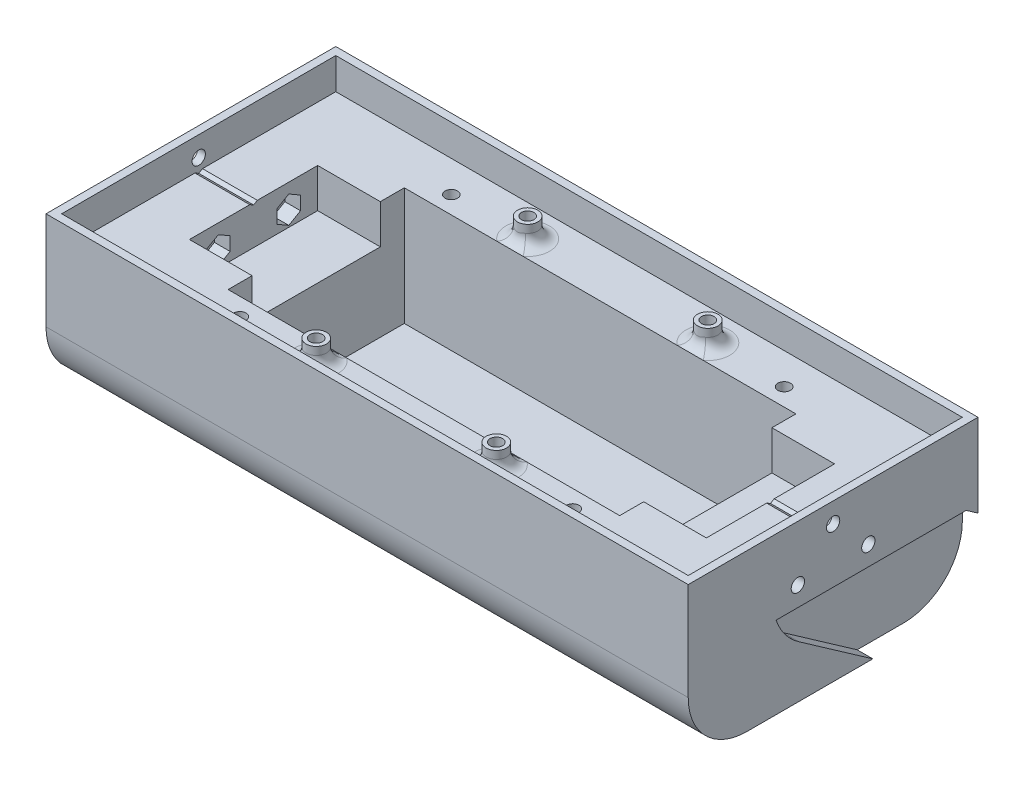
SolidWorks part; units mm, degrees
note: The reader was unsure of these and kept them because the rebuilt part matched: shared geometry of "Sketch2<3>", "Sketch2<4>", "Sketch2<5>", "Sketch4<7>", "Sketch4<4>", "Sketch4<5>", "Sketch4<6>", "Sketch4<8>", "Sketch4<9>".
ref_plane "Front Plane" through (0, 0, 0) normal (0, 0, 1) x (1, 0, 0)
ref_plane "Top Plane" through (0, 0, 0) normal (0, 1, 0) x (1, 0, 0)
ref_plane "Right Plane" through (0, 0, 0) normal (1, 0, 0) x (0, 0, -1)
sketch "Sketch2" plane through (0, 0, 0) normal (0, 1, 0) x (1, 0, 0)
  line L1 (-50, 22.5) -> (50, 22.5)
  line L2 (-50, 22.5) -> (-50, -22.5)
  line L3 (-50, -22.5) -> (50, -22.5)
  line L4 (50, 22.5) -> (50, -22.5)
  line L8 (-82, 37) -> (-82, -37)
  line L9 (-80, 35) -> (80, 35)
  line L10 (-80, 35) -> (-80, -35)
  line L11 (-80, -35) -> (80, -35)
  line L12 (80, 35) -> (80, -35)
  line L13 (-23, 27) -> (23, 27) construction
  line L14 (-23, 27) -> (-23, -27) construction
  line L15 (-23, -27) -> (23, -27) construction
  line L16 (23, 27) -> (23, -27) construction
  line L17 (-82, -37) -> (82, -37)
  line L18 (82, 37) -> (82, -37)
  line L19 (-82, 37) -> (82, 37)
  circle A0 centre (-23, 27) radius 1.6
  circle A1 centre (23, 27) radius 1.6
  circle A2 centre (23, -27) radius 1.6
  circle A3 centre (-23, -27) radius 1.6
  circle A4 centre (-23, 27) radius 2.6
  circle A5 centre (23, 27) radius 2.6
  circle A6 centre (23, -27) radius 2.6
  circle A7 centre (-23, -27) radius 2.6
  point P4 (0, 22.5)
  point P6 (-50, 0)
  point P11 (0, 35)
  point P12 (-80, 0)
  point P17 (0, 27)
  point P18 (-23, 0)
  dimension "D7" = 3.2
  dimension "D8" = 3.2
  dimension "D9" = 3.2
  dimension "D10" = 3.2
  dimension "D1" = 100
  dimension "D2" = 45
  dimension "D3" = 70
  dimension "D4" = 160
  dimension "D5" = 54
  dimension "D6" = 46
  dimension "D11" = 1
  dimension "D12" = 2
extrude "Boss-Extrude1" add sketch "Sketch2" along normal blind 40 contours L17 L18 L19 L8
extrude "Cut-Extrude1" cut sketch "Sketch2<3>" along normal through all from offset 2 contours L4 L1 L2 L3
sketch "Sketch2<3>" plane through (0, 0, 0) normal (0, 1, 0) x (1, 0, 0) same geometry as "Sketch2"
extrude "Cut-Extrude2" cut sketch "Sketch2<4>" against normal blind 8 from surface at 40 contours L11 L12 L9 L10 starting at face at (0, 40, 0)
sketch "Sketch2<4>" plane through (0, 0, 0) normal (0, 1, 0) x (1, 0, 0) same geometry as "Sketch2"
extrude "Boss-Extrude2" add sketch "Sketch2<5>" along normal blind 5 from surface at 32 contours A7 A3 | A6 A2 | A5 A1 | A4 A0 starting at face at (0, 32, 0)
sketch "Sketch2<5>" plane through (0, 0, 0) normal (0, 1, 0) x (1, 0, 0) same geometry as "Sketch2"
sketch "Sketch4" plane through (0, 0, 0) normal (1, 0, 0) x (0, 0, -1)
  line L0 (109.7184, -50.918) -> (0, 25.9077) construction
  line L1 (100.8853, -63.5329) -> (-8.8331, 13.2927)
  line L2 (118.5515, -38.303) -> (8.8331, 38.5226)
  line L3 (-9, 25.9077) -> (9, 25.9077) construction
  line L4 (-37, 0) -> (37, 0)
  line L5 (-37, 0) -> (-37, 20.9077)
  line L6 (-37, 20.9077) -> (37, 20.9077)
  line L7 (37, 0) -> (37, 20.9077)
  line L9 (0, 38.3718) -> (-3, 36.6397)
  line L10 (-3, 36.6397) -> (-3, 33.1756)
  line L11 (-3, 33.1756) -> (0, 31.4436)
  line L12 (0, 31.4436) -> (3, 33.1756)
  line L13 (3, 33.1756) -> (3, 36.6397)
  line L14 (3, 36.6397) -> (0, 38.3718)
  line L15 (9, 29.3718) -> (6, 27.6397)
  line L16 (6, 27.6397) -> (6, 24.1756)
  line L17 (6, 24.1756) -> (9, 22.4436)
  line L18 (9, 22.4436) -> (12, 24.1756)
  line L19 (12, 24.1756) -> (12, 27.6397)
  line L20 (12, 27.6397) -> (9, 29.3718)
  line L21 (-9, 29.3718) -> (-12, 27.6397)
  line L22 (-12, 27.6397) -> (-12, 24.1756)
  line L23 (-12, 24.1756) -> (-9, 22.4436)
  line L24 (-9, 22.4436) -> (-6, 24.1756)
  line L25 (-6, 24.1756) -> (-6, 27.6397)
  line L26 (-6, 27.6397) -> (-9, 29.3718)
  arc A0 (100.8853, -63.5329) -> (118.5515, -38.303) centre (109.7184, -50.918) ccw
  arc A1 (8.8331, 38.5226) -> (-8.8331, 13.2927) centre (0, 25.9077) ccw
  circle A2 centre (0, 34.9077) radius 1.7
  circle A3 centre (9, 25.9077) radius 1.7
  circle A4 centre (-9, 25.9077) radius 1.7
  circle A5 centre (0, 34.9077) radius 3 construction
  circle A6 centre (9, 25.9077) radius 3 construction
  circle A7 centre (-9, 25.9077) radius 3 construction
  point P2 (54.8592, -12.5052)
  point P17 (0, 25.9077)
  dimension "D4" = 3.4
  dimension "D5" = 3.4
  dimension "D6" = 15.4
  dimension "D8" = 3.4
  dimension "D9" = 6
  dimension "D10" = 6
  dimension "D11" = 6
  dimension "D1" = 5
  dimension "D2" = 9
  dimension "D3" = 9
  dimension "D7" = 35
extrude "Cut-Extrude3" cut sketch "Sketch4" against normal blind 4 from surface at 82 contours L6 A1 L1 L4 L2
extrude "Cut-Extrude7" cut sketch "Sketch4<7>" along normal blind 4 from surface at -82 contours L6 A1 L1 L4 L7 L2 starting at face at (-82, 20, 0)
sketch "Sketch4<7>" plane through (0, 0, 0) normal (1, 0, 0) x (0, 0, -1) same geometry as "Sketch4"
sketch "Sketch5" plane through (0, 32, 0) normal (0, 1, 0) x (1, 0, 0)
  line L0 (-80, -35) -> (-80, 35) construction
  line L1 (-66, 16.3738) -> (66, 16.3738)
  line L2 (-66, 16.3738) -> (-66, -16.3738)
  line L3 (-66, -16.3738) -> (66, -16.3738)
  line L4 (66, 16.3738) -> (66, -16.3738)
  line L6 (-42.5, 27) -> (42.5, 27) construction
  line L7 (-42.5, 27) -> (-42.5, -27) construction
  line L8 (-42.5, -27) -> (42.5, -27) construction
  line L9 (42.5, 27) -> (42.5, -27) construction
  circle A0 centre (-42.5, 27) radius 1.6
  circle A1 centre (42.5, 27) radius 1.6
  circle A2 centre (42.5, -27) radius 1.6
  circle A3 centre (-42.5, -27) radius 1.6
  point P4 (-66, 0)
  point P6 (0, 16.3738)
  point P13 (0, 27)
  point P14 (-42.5, 0)
  dimension "D4" = 3.2
  dimension "D5" = 3.2
  dimension "D6" = 3.2
  dimension "D7" = 3.2
  dimension "D1" = 14
  dimension "D2" = 54
  dimension "D3" = 85
extrude "Cut-Extrude10" cut sketch "Sketch5" against normal blind 10 contours L1 L4 L3 L2 | A0 | A1 | A2 | A3
extrude "Cut-Extrude4" cut sketch "Sketch4<4>" against normal through all both and the other way through all contours A2 | A3 | A4
sketch "Sketch4<4>" plane through (0, 0, 0) normal (1, 0, 0) x (0, 0, -1) same geometry as "Sketch4"
extrude "Cut-Extrude5" cut sketch "Sketch4<5>" along normal blind 4 from surface at 66 contours L25 L26 L21 L22 L23 L24 A4 | L19 L20 L15 L16 L17 L18 A3 starting at face at (66, 25.9077, -7.3)
sketch "Sketch4<5>" plane through (0, 0, 0) normal (1, 0, 0) x (0, 0, -1) same geometry as "Sketch4"
extrude "Cut-Extrude6" cut sketch "Sketch4<6>" along normal up to surface (30 mm away) from surface at 50 contours L13 L14 L9 L10 L11 L12 A2 up to face at (80, 34.9077, -1.7) starting at face at (50, 22, 0)
sketch "Sketch4<6>" plane through (0, 0, 0) normal (1, 0, 0) x (0, 0, -1) same geometry as "Sketch4"
extrude "Cut-Extrude8" cut sketch "Sketch4<8>" against normal blind 4 from surface at -66 contours L25 L26 L21 L22 L23 L24 A4 | L19 L20 L15 L16 L17 L18 A3 starting at face at (-66, 25.9077, -7.3)
sketch "Sketch4<8>" plane through (0, 0, 0) normal (1, 0, 0) x (0, 0, -1) same geometry as "Sketch4"
extrude "Cut-Extrude9" cut sketch "Sketch4<9>" against normal up to surface (30 mm away) from surface at -50 contours L13 L14 L9 L10 L11 L12 A2 up to face at (-80, 34.9077, -1.7) starting at face at (-50, 22, 0)
sketch "Sketch4<9>" plane through (0, 0, 0) normal (1, 0, 0) x (0, 0, -1) same geometry as "Sketch4"
fillet "Fillet1" radius 3 4 edges at (-23, 32, 29.6) (23, 32, 29.6) (23, 32, -24.4) (-23, 32, -24.4)
fillet "Fillet2" radius 15 2 edges at (0, 0, -37) (0, 0, 37)
